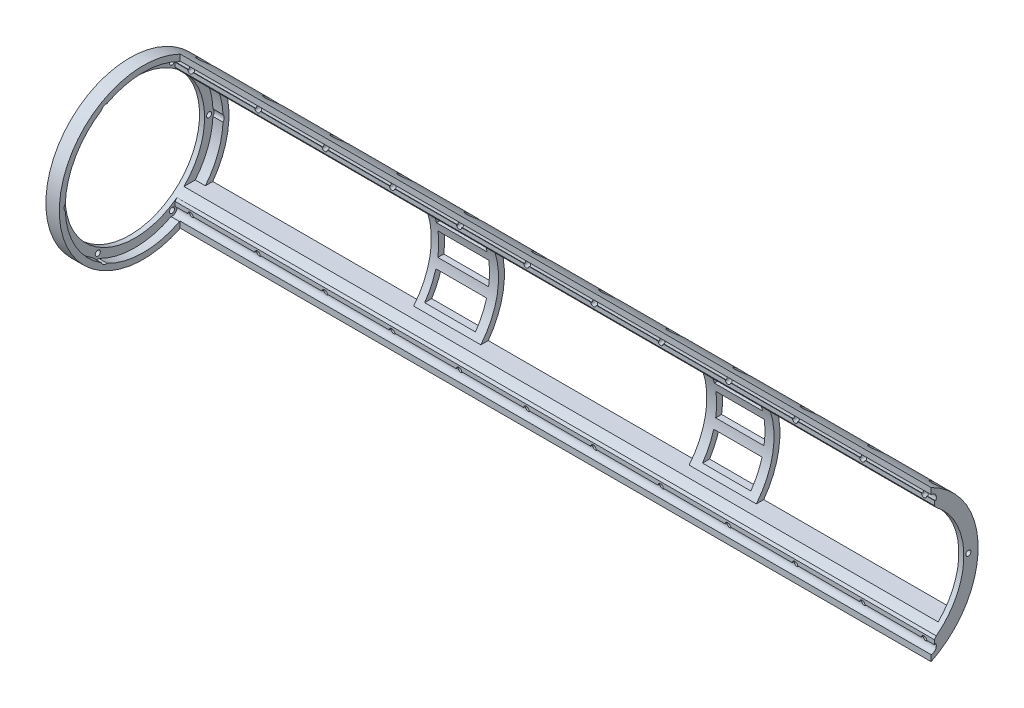
SolidWorks part; units mm, degrees
ref_plane "前视基准面" through (0, 0, 0) normal (0, 0, 1) x (1, 0, 0)
ref_plane "上视基准面" through (0, 0, 0) normal (0, 1, 0) x (1, 0, 0)
ref_plane "右视基准面" through (0, 0, 0) normal (1, 0, 0) x (0, 0, -1)
other "Configuration Table"
sketch "草图1" plane through (0, 0, 0) normal (1, 0, 0) x (0, 0, -1)
  line L0 (0, 0) -> (22, 0)
  line L1 (22, 0) -> (24, 0)
  line L2 (24, -39.8278) -> (24, -34.5778)
  line L3 (22, 40.9664) -> (22, 44.8999)
  line L5 (24, 39.8278) -> (24, 34.5778)
  line L6 (24, -34.5778) -> (31.0907, -34.5778)
  line L7 (24, 34.5778) -> (31.0907, 34.5778)
  line L8 (22, -40.9664) -> (22, -44.8999)
  arc A0 (22, -44.8999) -> (22, 44.8999) centre (0, 0) ccw
  arc A1 (22, -40.9664) -> (24, -39.8278) centre (0, 0) ccw
  arc A2 (24, 39.8278) -> (22, 40.9664) centre (0, 0) ccw
  arc A3 (31.0907, -34.5778) -> (31.0907, 34.5778) centre (0, 0) ccw
  dimension "D1" = 46.5
  dimension "D2" = 50
extrude "凸台-拉伸1" add sketch "草图1" along normal blind 455 contours A3 L7 L5 A2 L3 A0 L8 A1 L2 L6
sketch "草图2" plane through (0, 0, 0) normal (-1, 0, 0) x (0, 0, 1)
  line L0 (-24, -34.5778) -> (-31.0907, -34.5778)
  line L2 (-24, 34.5778) -> (-31.0907, 34.5778)
  arc A0 (-25.0521, 33.0854) -> (-25.0511, -33.0861) centre (0, 0) ccw
  arc A1 (-25.0521, 33.0854) -> (-24, 34.5778) centre (-26.8663, 35.4814) ccw
  arc A2 (-24, -34.5778) -> (-25.0511, -33.0861) centre (-26.8628, -35.4789) ccw
  arc A3 (-31.0907, 34.5778) -> (-31.0907, -34.5778) centre (0, 0) ccw
  dimension "D1" = 41.5
extrude "凸台-拉伸2" add sketch "草图2" against normal blind 3
sketch "草图3" plane through (0, 0, 0) normal (-1, 0, 0) x (0, 0, 1)
  circle A0 centre (-44.18, 0) radius 1.51
  circle A1 centre (-22.09, 38.261) radius 1.51
  circle A2 centre (22.09, 38.261) radius 1.51
  circle A3 centre (44.18, 0) radius 1.51
  circle A4 centre (22.09, -38.261) radius 1.51
  circle A5 centre (-22.09, -38.261) radius 1.51
  arc A6 (-25.0521, 33.0854) -> (-25.0511, -33.0861) centre (0, 0) ccw construction
  point P15 (0, 0)
  dimension "D1" = 3.02
  dimension "D3" = 44.18
  dimension "D2" = 6
extrude "切除-拉伸1" cut sketch "草图3" against normal blind 10 contours A0
sketch "草图5" plane through (3, 0, 0) normal (1, 0, 0) x (0, 0, -1)
  line L0 (44.18, 0) -> (44.18, 3)
  line L1 (44.18, 3) -> (44.18, -3)
  arc A0 (44.18, -3) -> (44.18, 3) centre (44.18, 0) ccw
  dimension "D1" = 3
extrude "切除-拉伸7" cut sketch "草图5" along normal blind 6 contours L1 A0
sketch "草图7" plane through (0, 0, -24) normal (0, 0, 1) x (1, 0, 0)
  line L0 (9, 0) -> (9, 29.5)
  line L1 (9, 1.9509) -> (9, -1.9509) construction
  line L2 (9, 0) -> (9, -29.5)
  line L3 (9, 29.5) -> (133, 29.5)
  line L4 (133, 29.5) -> (133, -29.5)
  line L5 (133, -29.5) -> (9, -29.5)
  line L6 (133, 29.5) -> (173, 29.5)
  line L7 (173, 29.5) -> (173, -29.5)
  line L8 (173, -29.5) -> (297, -29.5)
  line L9 (297, -29.5) -> (297, 29.5)
  line L10 (297, 29.5) -> (173, 29.5)
  line L11 (297, 29.5) -> (337, 29.5)
  line L12 (337, 29.5) -> (337, -29.5)
  line L13 (337, -29.5) -> (436.4929, -29.5)
  line L14 (436.4929, -29.5) -> (455, -29.5)
  line L15 (455, -34.5778) -> (455, 34.5778) construction
  line L16 (455, -29.5) -> (455, 29.5)
  line L17 (455, 29.5) -> (337, 29.5)
  line L31 (137.3955, 25.2167) -> (167.6252, 25.2167)
  line L32 (137.3955, 25.2167) -> (137.3955, 11.0725)
  line L33 (137.3955, 11.0725) -> (167.6252, 11.0725)
  line L34 (167.6252, 25.2167) -> (167.6252, 11.0725)
  line L35 (137.3955, -26.6453) -> (167.6252, -26.6453)
  line L36 (137.3955, -26.6453) -> (137.3955, -12.5012)
  line L37 (137.3955, -12.5012) -> (167.6252, -12.5012)
  line L38 (167.6252, -26.6453) -> (167.6252, -12.5012)
  line L39 (137.3955, 6.3578) -> (167.6252, 6.3578)
  line L40 (137.3955, 6.3578) -> (137.3955, -7.2318)
  line L41 (137.3955, -7.2318) -> (167.6252, -7.2318)
  line L42 (167.6252, 6.3578) -> (167.6252, -7.2318)
  line L43 (302.8225, 25.2167) -> (331.5768, 25.2167)
  line L44 (302.8225, 25.2167) -> (302.8225, 11.0725)
  line L45 (302.8225, 11.0725) -> (331.5768, 11.0725)
  line L46 (331.5768, 25.2167) -> (331.5768, 11.0725)
  line L47 (302.8225, 6.3578) -> (331.5768, 6.3578)
  line L48 (302.8225, 6.3578) -> (302.8225, -7.2318)
  line L49 (302.8225, -7.2318) -> (331.5768, -7.2318)
  line L50 (331.5768, 6.3578) -> (331.5768, -7.2318)
  line L51 (302.8225, -12.5012) -> (331.5768, -12.5012)
  line L52 (302.8225, -12.5012) -> (302.8225, -26.6453)
  line L53 (302.8225, -26.6453) -> (331.5768, -26.6453)
  line L54 (331.5768, -12.5012) -> (331.5768, -26.6453)
  dimension "D1" = 59
  dimension "D2" = 124
extrude "切除-拉伸8" cut sketch "草图7" against normal blind 100 contours L5 L4 L3 L0 L2 | L34 L31 L32 L33 | L9 L10 L7 L8 | L46 L43 L44 L45 | L16 L17 L12 L13 L14 | L39 L42 L41 L40 | L37 L38 L35 L36 | L47 L50 L49 L48 | L51 L54 L53 L52
sketch "草图8" plane through (0, 0, -24) normal (0, 0, 1) x (1, 0, 0)
  line L0 (0, 37.2028) -> (12, 37.2028)
  line L1 (0, 39.8278) -> (0, 34.5778) construction
  circle A0 centre (12, 37.2028) radius 1.55
sketch "草图9" plane through (0, 0, -24) normal (0, 0, 1) x (1, 0, 0)
  line L0 (0, 0) -> (155.2462, 0)
  line L2 (155.2462, 0) -> (155.2462, 14.6955)
  line L3 (155.2462, 14.6955) -> (0, 14.6955)
  line L4 (0, 33.0854) -> (0, -33.0861) construction
  line L5 (0, 14.6955) -> (0, 0)
  circle A0 centre (12, -37.2028) radius 1.55
extrude "切除-拉伸11" cut sketch "草图9" against normal through all contours A0
sketch "草图10" plane through (0, 0, -24) normal (0, 0, 1) x (1, 0, 0)
extrude "切除-拉伸12" cut sketch "草图8" against normal through all contours A0
sketch "草图12" plane through (455, 0, 0) normal (1, 0, 0) x (0, 0, -1)
  line L0 (22, 44.8999) -> (22, 40.9664)
  line L1 (22, -44.8999) -> (22, -40.9664)
  line L2 (24, -34.5778) -> (24, -39.8278)
  line L3 (24, -39.8278) -> (24, -34.5778) construction
  line L4 (24, 39.8278) -> (24, 34.5778)
  arc A0 (22, -44.8999) -> (22, 44.8999) centre (0, 0) ccw
  arc A1 (22, -40.9664) -> (22, 40.9664) centre (0, 0) ccw
  arc A2 (24.8085, -33.2684) -> (24.8077, 33.269) centre (0, 0) ccw
  circle A3 centre (26.4304, 35.1741) radius 2.5025
  arc A4 (25.0511, -33.0861) -> (27.9336, -37.1748) centre (26.4303, -35.1742) ccw
extrude "凸台-拉伸3" add sketch "草图12" against normal blind 3 contours A1 L0 A0 L1
sketch "草图14" plane through (455, 0, 0) normal (1, 0, 0) x (0, 0, -1)
  line L0 (31.0907, 34.5778) -> (24, 34.5778)
  line L1 (31.0907, -34.5778) -> (24, -34.5778)
  line L2 (24, -34.5778) -> (25.0511, -33.0861)
  line L3 (24, 34.5778) -> (25.0521, 33.0854)
  arc A0 (25.0511, -33.0861) -> (25.0521, 33.0854) centre (0, 0) ccw
  arc A1 (31.0907, -34.5778) -> (31.0907, 34.5778) centre (0, 0) ccw
extrude "凸台-拉伸4" add sketch "草图14" against normal blind 3
sketch "草图15" plane through (0, 0, 0) normal (-1, 0, 0) x (0, 0, 1)
  circle A0 centre (-44.18, 0) radius 1.51
extrude "切除-拉伸13" cut sketch "草图15" against normal blind 600
sketch "草图18" plane through (452, 0, 0) normal (-1, 0, 0) x (0, 0, 1)
  line L0 (-35.9444, -29.5) -> (-29.189, -29.5)
  line L1 (-35.9444, 29.5) -> (-29.189, 29.5)
  line L6 (-40.3702, -29.5) -> (-35.9444, -29.5)
  line L7 (-31.0907, -34.5778) -> (-24, -34.5778)
  line L8 (-24, -34.5778) -> (-25.0511, -33.0861)
  line L9 (-25.0521, 33.0854) -> (-24, 34.5778)
  line L10 (-24, 34.5778) -> (-31.0907, 34.5778)
  line L11 (-35.9444, 29.5) -> (-40.3702, 29.5)
  line L13 (-31.0907, -34.5778) -> (-24, -34.5778)
  line L14 (-24, -34.5778) -> (-25.0511, -33.0861)
  line L15 (-25.0521, 33.0854) -> (-24, 34.5778)
  line L16 (-24, 34.5778) -> (-31.0907, 34.5778)
  arc A0 (-29.189, -29.5) -> (-25.0511, -33.0861) centre (0, 0) ccw
  arc A4 (-40.3702, 29.5) -> (-40.3702, -29.5) centre (0, 0) ccw
  arc A5 (-35.9444, -29.5) -> (-31.0907, -34.5778) centre (0, 0) ccw
  arc A6 (-25.0521, 33.0854) -> (-25.0511, -33.0861) centre (0, 0) ccw
  arc A7 (-31.0907, 34.5778) -> (-35.9444, 29.5) centre (0, 0) ccw
  arc A9 (-35.9444, -29.5) -> (-31.0907, -34.5778) centre (0, 0) ccw
  arc A10 (-25.0521, 33.0854) -> (-29.189, 29.5) centre (0, 0) ccw
  arc A11 (-31.0907, 34.5778) -> (-35.9444, 29.5) centre (0, 0) ccw
  dimension "D1" = 0
extrude "凸台-拉伸5" add sketch "草图18" along normal up to surface (449 mm away) up to face at (3, 0, -42.67)
sketch "草图16" plane through (0, 0, -24) normal (0, 0, 1) x (1, 0, 0)
  line L0 (12, 37.2028) -> (-49988, 37.2028) construction
  line L1 (455, 39.8278) -> (455, 34.5778) construction
  line L2 (0, 0) -> (-50000, 0) construction
  circle A0 centre (12, 37.2028) radius 4
  circle A1 centre (448.8, 37.2028) radius 4
  circle A2 centre (448.8, -37.2028) radius 4
  dimension "D1" = 8
  dimension "D2" = 6.2
extrude "切除-拉伸14" cut sketch "草图16" against normal blind 11 from offset 4 offset against normal yes
pattern_linear "阵列(线性)2" count 11 spacing 40 along (1, 0, 0) of "切除-拉伸11", "切除-拉伸14"
sketch "草图17" plane through (0, 0, -24) normal (0, 0, 1) x (1, 0, 0)
  circle A0 centre (12, -37.2028) radius 4
  dimension "D1" = 8
extrude "切除-拉伸15" cut sketch "草图17" against normal blind 11 from offset 4 offset against normal yes
pattern_linear "阵列(线性)3" count 11 spacing 40 along (1, 0, 0) of "切除-拉伸12", "切除-拉伸15"
sketch "草图19" plane through (0, 0, 0) normal (1, 0, 0) x (0, 0, -1)
  circle A0 centre (0, 0) radius 46.5
  circle A1 centre (0, 0) radius 50
  dimension "D1" = 100
  dimension "D2" = 93
extrude "凸台-拉伸6" add sketch "草图19" along normal blind 8
sketch "草图22" plane through (0, 0, 0) normal (1, 0, 0) x (0, 0, -1)
  circle A0 centre (0, 0) radius 46.5
  circle A1 centre (0, 0) radius 41.5
extrude "凸台-拉伸7" add sketch "草图22" along normal blind 3
sketch "草图23" plane through (0, 0, 0) normal (1, 0, 0) x (0, 0, -1)
  circle A0 centre (44.18, 0) radius 1.525
  circle A2 centre (22.0905, -38.2601) radius 1.525
  circle A3 centre (-22.0885, -38.2601) radius 1.525
  circle A4 centre (-44.178, 0) radius 1.525
  circle A5 centre (-22.0885, 38.2601) radius 1.525
  circle A6 centre (22.0905, 38.2601) radius 1.525
  point P19 (0.001, 0)
  dimension "D1" = 3.05
  dimension "D2" = 6
extrude "切除-拉伸16" cut sketch "草图23" along normal blind 3
sketch "草图25" plane through (0, 0, 0) normal (1, 0, 0) x (0, 0, -1)
  line L0 (44.18, 3) -> (44.18, -3)
  arc A0 (44.18, -3) -> (44.18, 3) centre (44.18, 0) ccw
  point P6 (44.18, 0)
ref_plane "基准面1" through (3, 0, 0) normal (1, 0, 0) x (0, 0, -1)
sketch "草图26" plane through (3, 0, 0) normal (1, 0, 0) x (0, 0, -1)
  line L0 (44.18, -3) -> (44.18, 3)
  line L1 (19.4924, -39.7601) -> (24.6886, -36.7601)
  line L2 (-24.6866, -36.7601) -> (-19.4904, -39.7601)
  line L3 (-44.178, 3) -> (-44.178, -3)
  line L4 (-19.4904, 39.7601) -> (-24.6866, 36.7601)
  line L5 (24.6886, 36.7601) -> (19.4924, 39.7601)
  arc A0 (44.18, -3) -> (44.18, 3) centre (44.18, 0) ccw
  arc A3 (19.4924, -39.7601) -> (24.6886, -36.7601) centre (22.0905, -38.2601) ccw
  arc A5 (-24.6866, -36.7601) -> (-19.4904, -39.7601) centre (-22.0885, -38.2601) ccw
  arc A7 (-44.178, 3) -> (-44.178, -3) centre (-44.178, 0) ccw
  arc A9 (-19.4904, 39.7601) -> (-24.6866, 36.7601) centre (-22.0885, 38.2601) ccw
  arc A11 (24.6886, 36.7601) -> (19.4924, 39.7601) centre (22.0905, 38.2601) ccw
  point P7 (44.18, 0)
  point P37 (0.001, 0)
  dimension "D1" = 6
extrude "切除-拉伸17" cut sketch "草图26" along normal up to next
sketch "草图27" plane through (0, 0, 0) normal (0, 0, 1) x (1, 0, 0)
  line L0 (455, 37.1577) -> (413.5493, 37.1577) construction
  line L1 (455, 37.1577) -> (455, 34.5778) construction
  line L4 (542.4621, -0.0004) -> (367.5379, -0.0004) construction
  circle A0 centre (448.8, 37.1577) radius 1.55
  circle A1 centre (448.8, -37.1584) radius 1.55
  point P10 (455, -0.0004)
  dimension "D1" = 3.1
  dimension "D2" = 6.2
extrude "切除-拉伸18" cut sketch "草图27" against normal up to next
